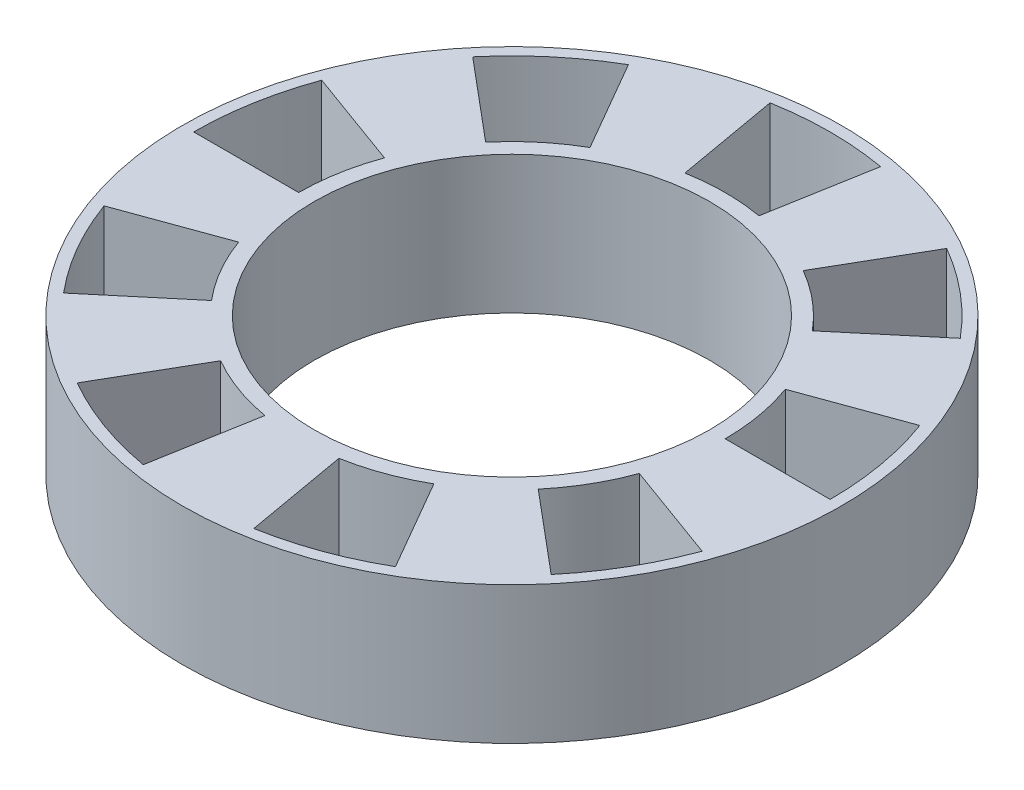
SolidWorks part; units mm, degrees
ref_plane "Front Plane" through (0, 0, 0) normal (0, 0, 1) x (1, 0, 0)
ref_plane "Top Plane" through (0, 0, 0) normal (0, 1, 0) x (1, 0, 0)
ref_plane "Right Plane" through (0, 0, 0) normal (1, 0, 0) x (0, 0, -1)
sketch "Sketch1" plane through (0, 0, 0) normal (0, 1, 0) x (1, 0, 0)
  circle A0 centre (0, 0) radius 44.45
  circle A1 centre (0, 0) radius 26.67
  dimension "D1" = 17.78
  dimension "D2" = 53.34
extrude "Boss-Extrude1" add sketch "Sketch1" along normal blind 18.542
sketch "Sketch2" plane through (0, 18.542, 0) normal (0, 1, 0) x (1, 0, 0)
  line L0 (-28.7608, 0) -> (-42.9222, 0)
  line L1 (-27.0264, 9.8368) -> (-40.3337, 14.6802)
  circle A0 centre (0, 0) radius 26.67 construction
  arc A1 (-27.0264, 9.8368) -> (-28.7608, 0) centre (0, 0) ccw
  arc A2 (-40.3337, 14.6802) -> (-42.9222, 0) centre (0, 0) ccw
  dimension "D1" = 28.7608
  dimension "D2" = 14.1613
  dimension "D3" = 20
extrude "Cut-Extrude1" cut sketch "Sketch2" against normal up to next
pattern_circular "CirPattern1" count 9 over 360 about axis through (0, 18.542, 0) along (0, -1, 0) of "Cut-Extrude1"
sketch "Sketch3" plane through (0, 18.542, 0) normal (0, 1, 0) x (1, 0, 0)
  line L0 (-38.4948, 22.225) -> (0, 0) construction
  line L1 (-27.0264, 9.8368) -> (-40.3337, 14.6802) construction
  circle A0 centre (0, 0) radius 44.45 construction
  dimension "D1" = 10
